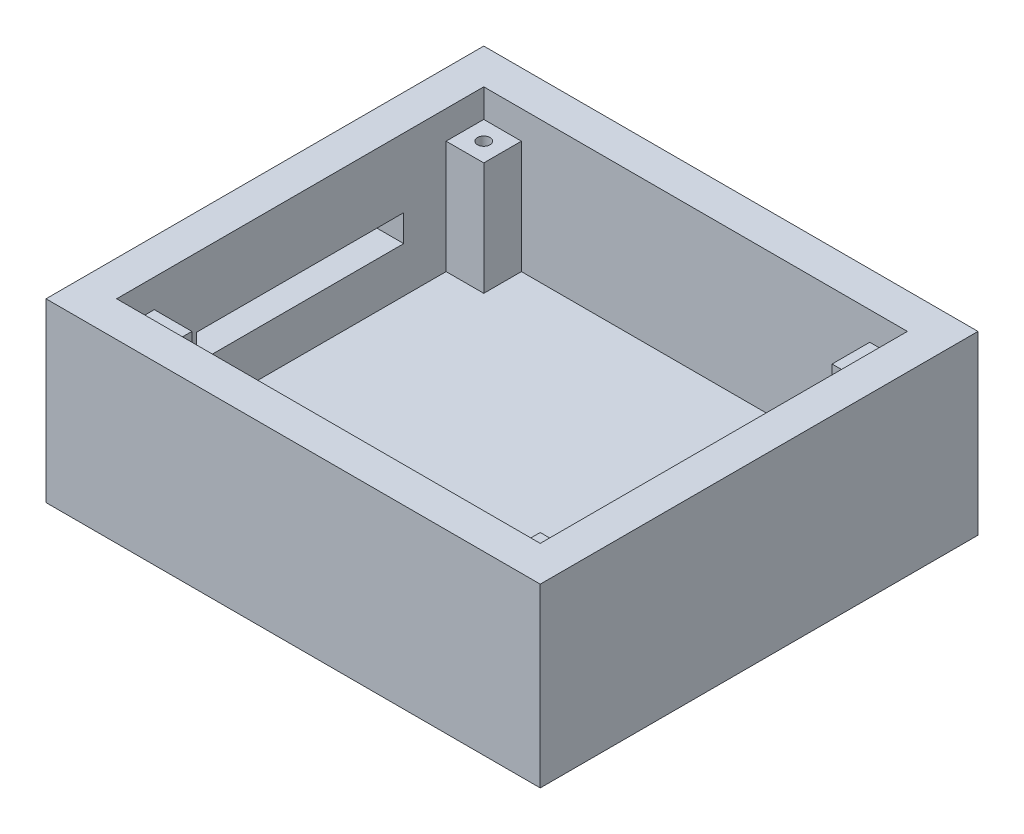
SolidWorks part; units mm, degrees
ref_plane "Front Plane" through (0, 0, 0) normal (0, 0, 1) x (1, 0, 0)
ref_plane "Top Plane" through (0, 0, 0) normal (0, 1, 0) x (1, 0, 0)
ref_plane "Right Plane" through (0, 0, 0) normal (1, 0, 0) x (0, 0, -1)
sketch "Sketch1" plane through (0, 0, 0) normal (0, 1, 0) x (1, 0, 0)
  line L0 (-57.15, 0) -> (-61.9125, 0) construction
  line L1 (-57.15, 49.53) -> (57.15, 49.53)
  line L2 (-57.15, 49.53) -> (-57.15, -49.53)
  line L3 (-57.15, -49.53) -> (57.15, -49.53)
  line L4 (57.15, 49.53) -> (57.15, -49.53)
  line L5 (-57.15, 49.53) -> (57.15, -49.53) construction
  line L6 (-57.15, -49.53) -> (57.15, 49.53) construction
  line L7 (57.15, 0) -> (61.9125, 0) construction
  line L8 (-66.675, 59.055) -> (-57.15, 59.055)
  line L9 (-66.675, 59.055) -> (-66.675, -59.055)
  line L10 (-66.675, -59.055) -> (-57.15, -59.055)
  line L11 (-57.15, 59.055) -> (-57.15, -59.055)
  line L12 (-66.675, 59.055) -> (-57.15, -59.055) construction
  line L13 (-66.675, -59.055) -> (-57.15, 59.055) construction
  line L14 (-57.15, 59.055) -> (57.15, 59.055)
  line L15 (66.675, 59.055) -> (57.15, 59.055)
  line L16 (66.675, 59.055) -> (66.675, -59.055)
  line L17 (66.675, -59.055) -> (57.15, -59.055)
  line L18 (57.15, 59.055) -> (57.15, -59.055)
  line L19 (66.675, 59.055) -> (57.15, -59.055) construction
  line L20 (66.675, -59.055) -> (57.15, 59.055) construction
  line L21 (-57.15, -59.055) -> (57.15, -59.055)
  point P0 (0, 0)
  dimension "D1" = 114.3
  dimension "D2" = 99.06
  dimension "D3" = 4.7625
  dimension "D4" = 118.11
  dimension "D5" = 4.7625
  dimension "D6" = 118.11
extrude "Boss-Extrude1" add sketch "Sketch1" along normal blind 9.525 contours L4 L1 L2 L3 region at (0, 0, 0)
extrude "Boss-Extrude2" add sketch "Sketch1<3>" along normal blind 47.625 contours L11 L8 L9 L10 L2 | L18 L14 L11 L1 | L15 L18 L4 L17 L16 | L11 L21 L18 L3 region at (0, 0, -54.2925) region at (-61.9125, 0, 0) region at (61.9125, 0, 0) region at (0, 0, 54.2925)
sketch "Sketch1<3>" plane through (0, 0, 0) normal (0, 1, 0) x (1, 0, 0) same geometry as "Sketch1"
sketch "Sketch3" plane through (0, 9.525, 0) normal (0, 1, 0) x (1, 0, 0)
  line L0 (-46.99, 44.45) -> (-57.15, 44.45) construction
  line L1 (-57.15, 49.53) -> (-46.99, 49.53)
  line L2 (-57.15, 49.53) -> (-57.15, 39.37)
  line L3 (-57.15, 39.37) -> (-46.99, 39.37)
  line L4 (-46.99, 49.53) -> (-46.99, 39.37)
  line L5 (57.15, 49.53) -> (46.99, 49.53)
  line L6 (57.15, 49.53) -> (57.15, 39.37)
  line L7 (57.15, 39.37) -> (46.99, 39.37)
  line L8 (46.99, 49.53) -> (46.99, 39.37)
  line L9 (57.15, -49.53) -> (46.99, -49.53)
  line L10 (57.15, -49.53) -> (57.15, -39.37)
  line L11 (57.15, -39.37) -> (46.99, -39.37)
  line L12 (46.99, -49.53) -> (46.99, -39.37)
  line L13 (-57.15, -49.53) -> (-46.99, -49.53)
  line L14 (-57.15, -49.53) -> (-57.15, -39.37)
  line L15 (-57.15, -39.37) -> (-46.99, -39.37)
  line L16 (-46.99, -49.53) -> (-46.99, -39.37)
  line L17 (46.99, 44.45) -> (57.15, 44.45) construction
  line L18 (-46.99, -44.45) -> (-57.15, -44.45) construction
  line L19 (46.99, -44.45) -> (57.15, -44.45) construction
  circle A0 centre (-52.07, 44.45) radius 1.7018
  circle A1 centre (52.07, 44.45) radius 1.7018
  circle A2 centre (52.07, -44.45) radius 1.7018
  circle A3 centre (-52.07, -44.45) radius 1.7018
  dimension "D1" = 10.16
  dimension "D2" = 10.16
  dimension "D3" = 10.16
  dimension "D4" = 10.16
  dimension "D5" = 10.16
  dimension "D6" = 10.16
  dimension "D7" = 10.16
  dimension "D8" = 10.16
extrude "Boss-Extrude3" add sketch "Sketch3" along normal blind 30.48
sketch "Sketch5" plane through (-66.675, 0, 0) normal (-1, 0, 0) x (0, 0, 1)
  line L0 (-59.055, 0) -> (-59.055, 25.4) construction
  line L1 (-59.055, 47.625) -> (-59.055, 0) construction
  line L2 (-59.055, 25.4) -> (59.055, 25.4) construction
  line L3 (59.055, 47.625) -> (59.055, 0) construction
  line L5 (-27.94, 29.0195) -> (27.94, 29.0195)
  line L6 (-27.94, 29.0195) -> (-27.94, 21.7805)
  line L7 (-27.94, 21.7805) -> (27.94, 21.7805)
  line L8 (27.94, 29.0195) -> (27.94, 21.7805)
  line L9 (-27.94, 29.0195) -> (27.94, 21.7805) construction
  line L10 (-27.94, 21.7805) -> (27.94, 29.0195) construction
  point P5 (0, 25.4)
  dimension "D1" = 25.4
  dimension "D2" = 55.88
  dimension "D3" = 7.239
extrude "Cut-Extrude1" cut sketch "Sketch5" against normal blind 30.48
sketch "Sketch6" plane through (0, 0, -49.53) normal (0, 0, 1) x (1, 0, 0)
  line L0 (-46.99, 40.005) -> (-46.99, 47.625) construction
  line L1 (-57.15, 47.625) -> (57.15, 47.625) construction
